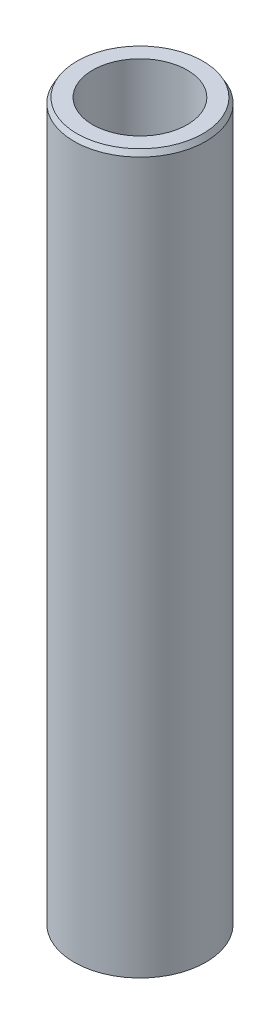
SolidWorks part; units mm, degrees
ref_plane "Front Plane" through (0, 0, 0) normal (0, 0, 1) x (1, 0, 0)
ref_plane "Top Plane" through (0, 0, 0) normal (0, 1, 0) x (1, 0, 0)
ref_plane "Right Plane" through (0, 0, 0) normal (1, 0, 0) x (0, 0, -1)
sketch "Sketch1" plane through (0, 0, 0) normal (0, 1, 0) x (1, 0, 0)
  circle A0 centre (0, 0) radius 55
  dimension "SHAFT_OD" = 110
extrude "Boss-Extrude1" add sketch "Sketch1" along normal blind 600
sketch "Sketch2" plane through (0, 0, 0) normal (0, 1, 0) x (1, 0, 0)
  circle A0 centre (0, 0) radius 39.4897
  dimension "BORE_D" = 78.9794
extrude "Cut-Extrude1" cut sketch "Sketch2" along normal through all
chamfer "Chamfer1" distance 4.2868 angle 30 2 edges at (0, 600, 55) (0, 0, 55) first distance on face at (0, 600, 55) first distance on face at (0, 0, 39.4897)
